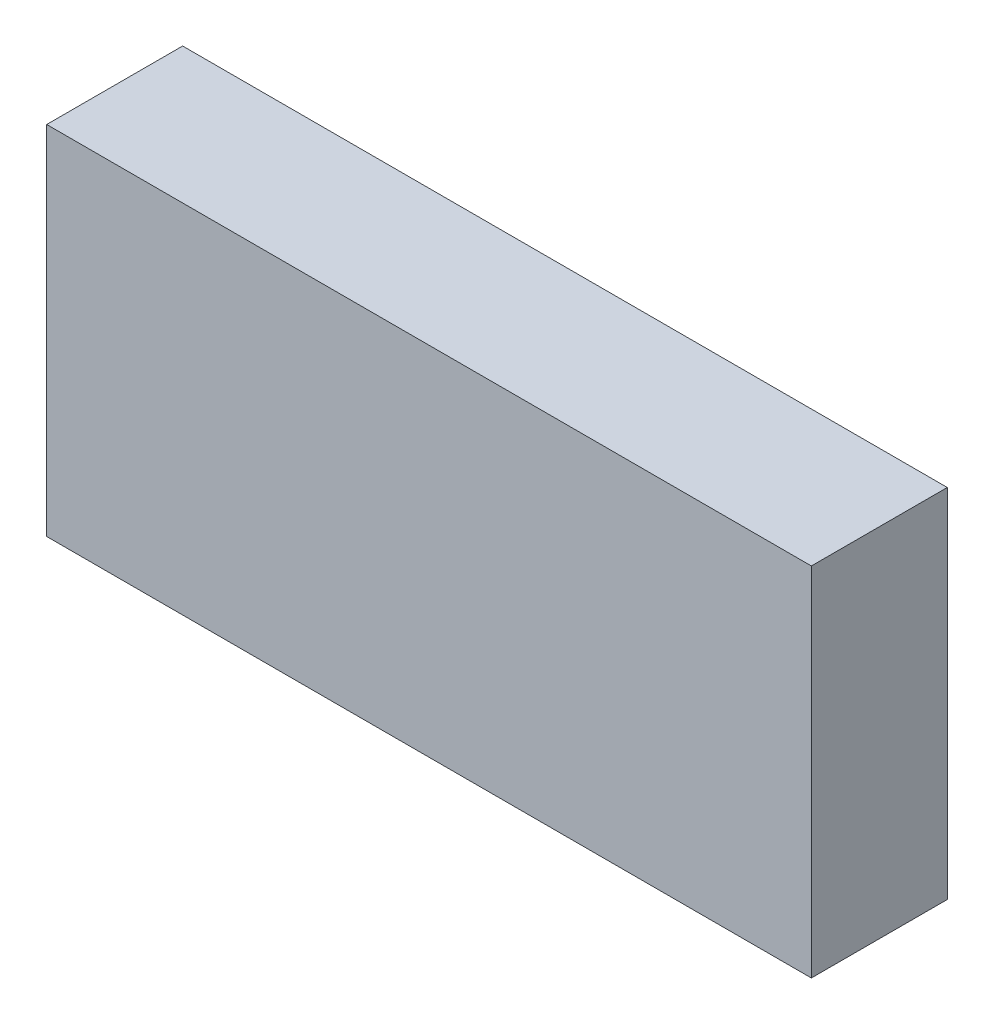
SolidWorks part; units mm, degrees
ref_plane "Front Plane" through (0, 0, 0) normal (0, 0, 1) x (1, 0, 0)
ref_plane "Top Plane" through (0, 0, 0) normal (0, 1, 0) x (1, 0, 0)
ref_plane "Right Plane" through (0, 0, 0) normal (1, 0, 0) x (0, 0, -1)
sketch "Sketch1" plane through (0, 0, 0) normal (0, 0, 1) x (1, 0, 0)
  line L1 (0, 0) -> (45, 0)
  line L2 (0, 0) -> (0, 21)
  line L3 (0, 21) -> (45, 21)
  line L4 (45, 0) -> (45, 21)
  dimension "D1" = 45
  dimension "D2" = 21
extrude "Boss-Extrude1" add sketch "Sketch1" along normal blind 8
sketch "Sketch2" plane through (0, 0, 8) normal (0, 0, 1) x (1, 0, 0)
  text T0 "Weapon ESC"
